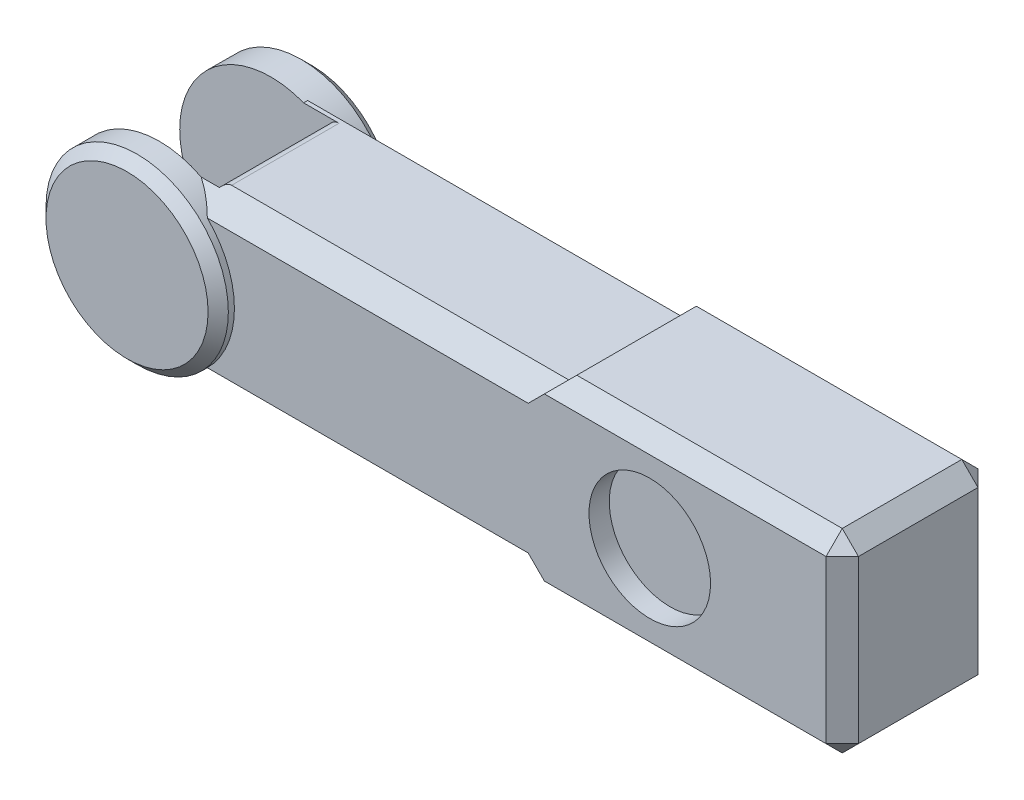
SolidWorks part; units mm, degrees
ref_plane "Plan de face" through (0, 0, 0) normal (0, 0, 1) x (1, 0, 0)
ref_plane "Plan de dessus" through (0, 0, 0) normal (0, 1, 0) x (1, 0, 0)
ref_plane "Plan de droite" through (0, 0, 0) normal (1, 0, 0) x (0, 0, -1)
sketch "Esquisse1" plane through (0, 0, 0) normal (0, 0, 1) x (1, 0, 0)
  line L0 (95, -48) -> (95, 48)
  line L1 (95, 48) -> (-50, 48)
  line L2 (-50, 48) -> (-50, 42)
  line L3 (-50, 42) -> (-233.8445, 42)
  line L4 (-250, 0) -> (0, 0) construction
  line L5 (-50, -42) -> (-233.8445, -42)
  line L6 (-50, -48) -> (-50, -42)
  line L7 (95, -48) -> (-50, -48)
  arc A0 (-233.8445, 42) -> (-233.8445, -42) centre (-250, 0) ccw
  dimension "D2" = 90
  dimension "D3" = 95
  dimension "D1" = 250
  dimension "D4" = 42
  dimension "D5" = 48
  dimension "D6" = 50
extrude "Boss.-Extru.1" add sketch "Esquisse1" along normal blind 75
sketch "Sketch3" plane through (0, 0, 75) normal (0, 0, 1) x (1, 0, 0)
  circle A0 centre (0, 0) radius 30
extrude "Cut-Extrude3" cut sketch "Sketch3" against normal blind 10
sketch "Esquisse2" plane through (0, 0, 75) normal (0, 0, 1) x (1, 0, 0)
  circle A0 centre (-250, 0) radius 45
extrude "Boss.-Extru.2" add sketch "Esquisse2" along normal blind 8
chamfer "Chanfrein1" distance 5 angle 45 1 edges at (-205, 0, 83)
sketch "Esquisse3" plane through (0, 0, 0) normal (0, 0, -1) x (-1, 0, 0)
  circle A0 centre (250, 0) radius 45
extrude "Boss.-Extru.3" add sketch "Esquisse3" along normal blind 8
chamfer "Chanfrein2" distance 5 angle 45 1 edges at (-295, 0, -8)
draft "Dépouille5" type of draft neutral plane draft angle 45 faces to draft 1 face at (-50, 45, 37.5) neutral plane through (-50, 42, 75) neutral plane normal (0, 1, 0) parameters "D1"=45
draft "Dépouille6" type of draft neutral plane draft angle 45 faces to draft 1 face at (-50, -45, 37.5) neutral plane through (-50, -42, 75) neutral plane normal (0, -1, 0) parameters "D1"=45
chamfer "Chanfrein4" distance 10 angle 45 4 edges
ref_plane "Plane1" through (0, 0, 12) normal (0, 0, -1) x (-1, 0, 0)
sketch "Sketch2" plane through (0, 0, 12) normal (0, 0, -1) x (-1, 0, 0)
  circle A0 centre (250, 0) radius 45
extrude "Cut-Extrude2" cut sketch "Sketch2" against normal blind 55
fillet "Fillet1" radius 5 2 edges
chamfer "Chamfer1" distance 8 angle 45 8 edges at (95, -48, 37.5) (25.5, -48, 0) (95, 0, 0) (25.5, 48, 0) (95, 48, 37.5) (25.5, 48, 75) (95, 0, 75) (25.5, -48, 75)
